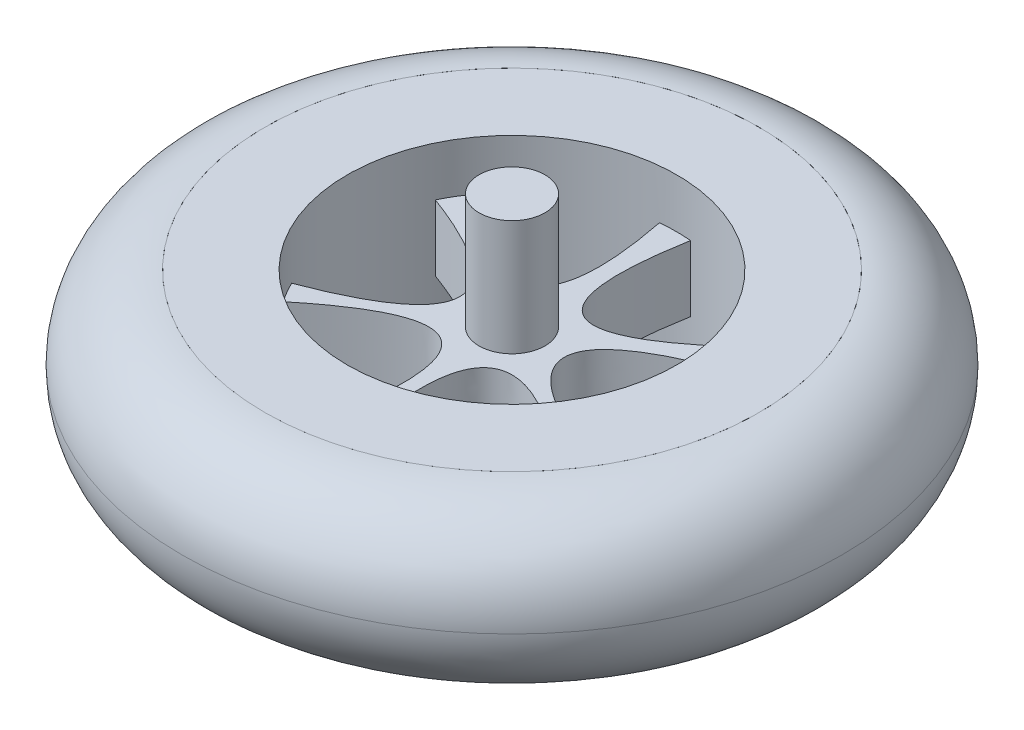
SolidWorks part; units mm, degrees
ref_plane "Alzado" through (0, 0, 0) normal (0, 0, 1) x (1, 0, 0)
ref_plane "Planta" through (0, 0, 0) normal (0, 1, 0) x (1, 0, 0)
ref_plane "Vista lateral" through (0, 0, 0) normal (1, 0, 0) x (0, 0, -1)
sketch "Croquis1" plane through (0, 0, 0) normal (0, 1, 0) x (1, 0, 0)
  circle A0 centre (0, 0) radius 15
  dimension "D1" = 30
extrude "Saliente-Extruir2" add sketch "Croquis1" along normal blind 5
sketch "Croquis3" plane through (0, 5, 0) normal (0, 1, 0) x (1, 0, 0)
  circle A0 centre (0, 0) radius 10
  dimension "D1" = 20
extrude "Cortar-Extruir2" cut sketch "Croquis3" against normal blind 3
sketch "Croquis4" plane through (0, 2, 0) normal (0, 1, 0) x (1, 0, 0)
  arc A0 (-1.0012, 9.9498) -> (-8.272, 5.6191) centre (0, 0) ccw
  circle A1 centre (0, 0) radius 10
  arc A2 (-9.0024, 4.354) -> (-8.9859, -4.388) centre (0, 0) ccw
  arc A3 (8.05, 5.9327) -> (0.8771, 9.9615) centre (0, 0) ccw
  arc A4 (8.9859, -4.388) -> (9.0024, 4.354) centre (0, 0) ccw
  arc A5 (0.8771, -9.9615) -> (8.272, -5.6191) centre (0, 0) ccw
  arc A6 (-8.272, -5.6191) -> (-0.711, -9.9747) centre (0, 0) ccw
  spline S0 degree 2 poles (-1.0012, 9.9498) (1.4305, -2.2931) (-8.272, 5.6191) knots 0 0 0 1 1 1
  spline S1 degree 2 poles (-9.0024, 4.354) (2.6349, 0.0127) (-8.9859, -4.388) knots 0 0 0 1 1 1
  spline S2 degree 2 poles (-8.272, -5.6191) (1.315, 2.2878) (-0.711, -9.9747) knots 0 0 0 1 1 1
  spline S3 degree 2 poles (0.8771, -9.9615) (-1.3796, 2.292) (8.272, -5.6191) knots 0 0 0 1 1 1
  spline S4 degree 2 poles (8.9859, -4.388) (-2.6349, 0.014) (9.0024, 4.354) knots 0 0 0 1 1 1
  spline S5 degree 2 poles (8.05, 5.9327) (-1.3066, -2.4272) (0.8771, 9.9615) knots 0 0 0 1 1 1
  dimension "D1" = 0
extrude "Cortar-Extruir3" cut sketch "Croquis4" against normal through all
sketch "Croquis5" plane through (0, 2, 0) normal (0, 1, 0) x (1, 0, 0)
  circle A0 centre (0, 0) radius 2
  dimension "D1" = 4
extrude "Saliente-Extruir3" add sketch "Croquis5" along normal blind 7
mirror "Simetría2" about plane through (0, 0, 0) normal (0, 1, 0) of "Saliente-Extruir3", "Cortar-Extruir3", "Cortar-Extruir2", "Saliente-Extruir2"
sketch "Croquis7" plane through (0, 0, 0) normal (0, 0, 1) x (1, 0, 0)
  line L0 (-15, 5) -> (-15, -5)
  line L1 (-15, -5) -> (-20, -5)
  line L2 (-20, -5) -> (-20, 5)
  line L3 (-20, 5) -> (-15, 5)
  line L4 (0, -11.7191) -> (0, 11.0726) construction
  dimension "D1" = 5
revolve "Revolución3" add sketch "Croquis7" angle 360 about L4 region at (-17.5, 0, 0)
fillet "Redondeo1" radius 5 2 edges at (0, -5, -20) (0, 5, -20)
